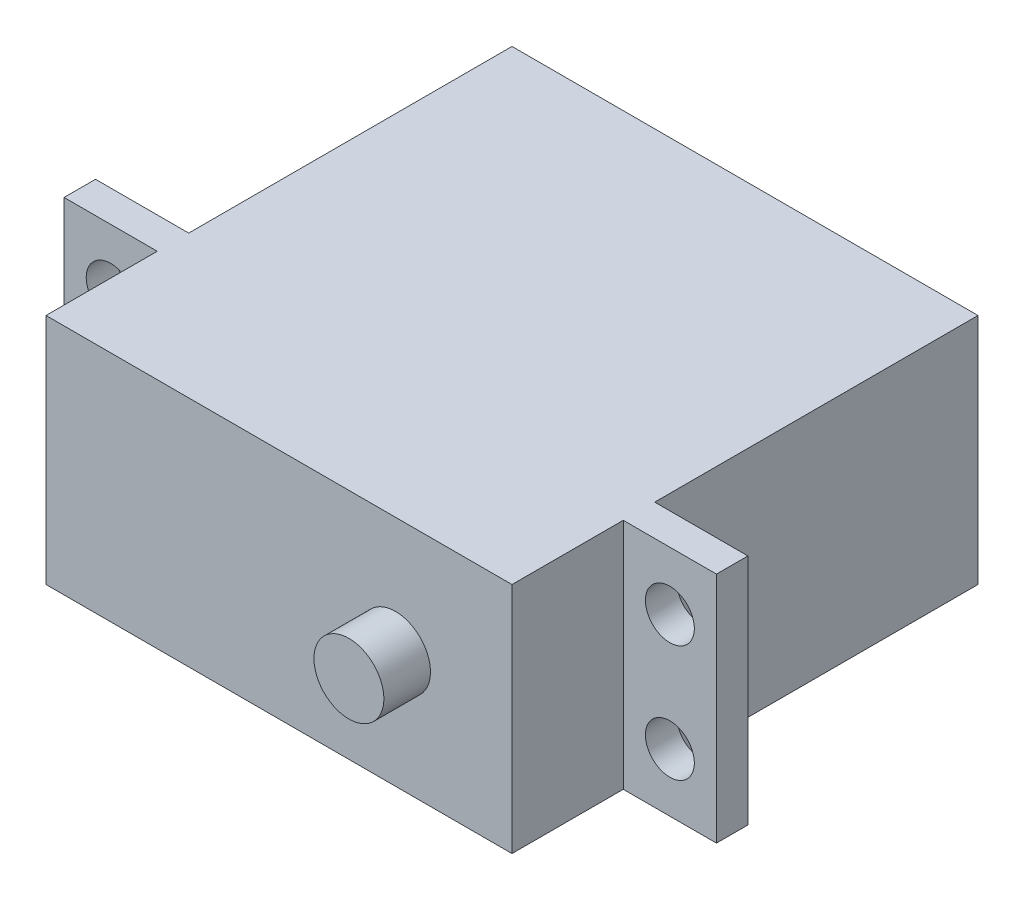
SolidWorks part; units mm, degrees
ref_plane "Front Plane" through (0, 0, 0) normal (0, 0, 1) x (1, 0, 0)
ref_plane "Top Plane" through (0, 0, 0) normal (0, 1, 0) x (1, 0, 0)
ref_plane "Right Plane" through (0, 0, 0) normal (1, 0, 0) x (0, 0, -1)
sketch "Sketch1" plane through (0, 0, 0) normal (0, 0, 1) x (1, 0, 0)
  line L1 (-20, -10) -> (20, -10)
  line L2 (-20, -10) -> (-20, 10)
  line L3 (-20, 10) -> (20, 10)
  line L4 (20, -10) -> (20, 10)
  line L5 (-20, -10) -> (20, 10) construction
  line L6 (-20, 10) -> (20, -10) construction
  point P0 (0, 0)
extrude "Boss-Extrude1" add sketch "Sketch1" along normal blind 40
sketch "Sketch2" plane through (0, 0, 0) normal (0, 0, 1) x (1, 0, 0)
  line L0 (20, 0) -> (10, 0) construction
  line L1 (20, -10) -> (20, 10) construction
  line L2 (10, 0) -> (10, -10) construction
  line L3 (-20, -10) -> (20, -10) construction
  circle A0 centre (10, 0) radius 3
extrude "Boss-Extrude2" add sketch "Sketch2" along normal blind 4 from surface starting at face at (0, 0, 40)
sketch "Sketch3" plane through (0, 0, 0) normal (0, 0, 1) x (1, 0, 0)
  line L0 (-28, 0) -> (-24, 0) construction
  line L1 (-28, -10) -> (28, -10)
  line L2 (-28, -10) -> (-28, 10)
  line L3 (-28, 10) -> (28, 10)
  line L4 (28, -10) -> (28, 10)
  line L5 (-28, -10) -> (28, 10) construction
  line L6 (-28, 10) -> (28, -10) construction
  line L7 (-24, 0) -> (-24, 5) construction
  line L8 (0, 0) -> (0, 5.4036) construction
  circle A0 centre (-24, 5) radius 2.1
  circle A1 centre (-24, -5) radius 2.1
  circle A2 centre (24, -5) radius 2.1
  circle A3 centre (24, 5) radius 2.1
  point P1 (0, 0)
extrude "Boss-Extrude3" add sketch "Sketch3" along normal blind 2.7 from offset 27.75
